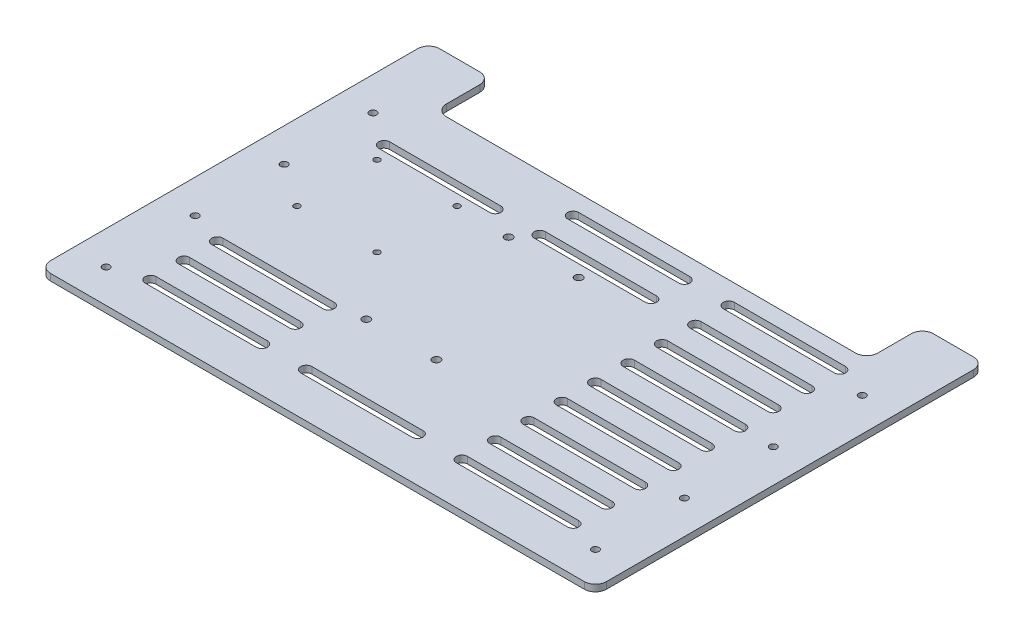
SolidWorks part; units mm, degrees
material "A-玻璃纤维"
ref_plane "前视基准面" through (0, 0, 0) normal (0, 0, 1) x (1, 0, 0)
ref_plane "上视基准面" through (0, 0, 0) normal (0, 1, 0) x (1, 0, 0)
ref_plane "右视基准面" through (0, 0, 0) normal (1, 0, 0) x (0, 0, -1)
other "Configuration Table"
sketch "草图1" plane through (0, 0, 0) normal (0, 1, 0) x (1, 0, 0)
  line L1 (-84.7342, 82.3595) -> (109.2658, 82.3595)
  line L2 (-112.7342, 55.552) -> (-112.7342, -67.6405)
  line L3 (-112.7342, -67.6405) -> (137.2658, -67.6405)
  line L4 (137.2658, 82.3595) -> (137.2658, -67.6405)
  line L5 (-112.7342, 55.552) -> (137.2658, -67.6405) construction
  line L6 (-112.7342, -67.6405) -> (137.2658, 82.3595) construction
  line L8 (-112.7342, 55.552) -> (-112.7342, 107.3595)
  line L9 (-112.7342, 107.3595) -> (-84.7342, 107.3595)
  line L10 (-84.7342, 82.3595) -> (-84.7342, 107.3595)
  line L12 (137.2658, 82.3595) -> (137.2658, 107.3595)
  line L13 (137.2658, 107.3595) -> (109.2658, 107.3595)
  line L14 (109.2658, 82.3595) -> (109.2658, 107.3595)
  point P0 (0, 0)
  dimension "D1" = 150
  dimension "D2" = 250
  dimension "D3" = 28
  dimension "D4" = 28
  dimension "D5" = 25
extrude "凸台-拉伸1" add sketch "草图1" along normal blind 3
fillet "圆角1" radius 5 8 edges at (137.2658, 1.5, 67.6405) (-112.7342, 1.5, 67.6405) (137.2658, 1.5, -107.3595) (109.2658, 1.5, -107.3595) (109.2658, 1.5, -82.3595) (-112.7342, 1.5, -107.3595) (-84.7342, 1.5, -107.3595) (-84.7342, 1.5, -82.3595)
sketch "草图4" plane through (0, 3, 0) normal (0, 1, 0) x (1, 0, 0)
  line L0 (57.2658, 72.3595) -> (107.2658, 72.3595) construction
  line L1 (57.2658, 74.8595) -> (107.2658, 74.8595)
  line L2 (57.2658, 69.8595) -> (107.2658, 69.8595)
  line L3 (57.2658, 57.3595) -> (107.2658, 57.3595) construction
  line L4 (104.2658, 82.3595) -> (-79.7342, 82.3595)
  line L5 (-112.7342, 102.3595) -> (-112.7342, -62.6405)
  line L6 (-107.7342, -67.6405) -> (132.2658, -67.6405)
  line L7 (137.2658, -62.6405) -> (137.2658, 102.3595)
  line L8 (104.2658, 82.3595) -> (-79.7342, 82.3595)
  line L9 (-112.7342, 102.3595) -> (-112.7342, -62.6405)
  line L11 (137.2658, -62.6405) -> (137.2658, 102.3595)
  line L12 (57.2658, 59.8595) -> (107.2658, 59.8595)
  line L13 (57.2658, 54.8595) -> (107.2658, 54.8595)
  line L14 (57.2658, 42.3595) -> (107.2658, 42.3595) construction
  line L15 (57.2658, 44.8595) -> (107.2658, 44.8595)
  line L16 (132.2658, 107.3595) -> (114.2658, 107.3595)
  line L17 (132.2658, 107.3595) -> (114.2658, 107.3595)
  line L18 (109.2658, 102.3595) -> (109.2658, 87.3595)
  line L19 (109.2658, 102.3595) -> (109.2658, 87.3595)
  line L20 (-84.7342, 87.3595) -> (-84.7342, 102.3595)
  line L21 (-84.7342, 87.3595) -> (-84.7342, 102.3595)
  line L22 (-89.7342, 107.3595) -> (-107.7342, 107.3595)
  line L23 (-89.7342, 107.3595) -> (-107.7342, 107.3595)
  line L24 (57.2658, 39.8595) -> (107.2658, 39.8595)
  line L25 (57.2658, 27.3595) -> (107.2658, 27.3595) construction
  line L26 (57.2658, 29.8595) -> (107.2658, 29.8595)
  line L27 (57.2658, 24.8595) -> (107.2658, 24.8595)
  line L28 (57.2658, 12.3595) -> (107.2658, 12.3595) construction
  line L29 (57.2658, 14.8595) -> (107.2658, 14.8595)
  line L30 (57.2658, 9.8595) -> (107.2658, 9.8595)
  line L31 (57.2658, -2.6405) -> (107.2658, -2.6405) construction
  line L32 (57.2658, -0.1405) -> (107.2658, -0.1405)
  line L33 (57.2658, -5.1405) -> (107.2658, -5.1405)
  line L34 (57.2658, -17.6405) -> (107.2658, -17.6405) construction
  line L35 (57.2658, -15.1405) -> (107.2658, -15.1405)
  line L36 (57.2658, -20.1405) -> (107.2658, -20.1405)
  line L37 (57.2658, -32.6405) -> (107.2658, -32.6405) construction
  line L38 (57.2658, -30.1405) -> (107.2658, -30.1405)
  line L39 (57.2658, -35.1405) -> (107.2658, -35.1405)
  line L40 (57.2658, -47.6405) -> (107.2658, -47.6405) construction
  line L41 (57.2658, -45.1405) -> (107.2658, -45.1405)
  line L42 (57.2658, -50.1405) -> (107.2658, -50.1405)
  line L52 (-12.7342, 72.3595) -> (37.2658, 72.3595) construction
  line L53 (-12.7342, 74.8595) -> (37.2658, 74.8595)
  line L54 (-12.7342, 69.8595) -> (37.2658, 69.8595)
  line L55 (-12.7342, 57.3595) -> (37.2658, 57.3595) construction
  line L56 (-12.7342, 59.8595) -> (37.2658, 59.8595)
  line L57 (-12.7342, 54.8595) -> (37.2658, 54.8595)
  line L58 (-82.7342, 72.3595) -> (-32.7342, 72.3595) construction
  line L59 (-82.7342, 74.8595) -> (-32.7342, 74.8595)
  line L60 (-82.7342, 69.8595) -> (-32.7342, 69.8595)
  line L61 (-82.7342, 57.3595) -> (-32.7342, 57.3595) construction
  line L62 (-82.7342, 59.8595) -> (-32.7342, 59.8595)
  line L63 (-82.7342, 54.8595) -> (-32.7342, 54.8595)
  line L64 (-12.7342, -47.6405) -> (37.2658, -47.6405) construction
  line L65 (-12.7342, -45.1405) -> (37.2658, -45.1405)
  line L66 (-12.7342, -50.1405) -> (37.2658, -50.1405)
  line L76 (-82.7342, -47.6405) -> (-32.7342, -47.6405) construction
  line L77 (-82.7342, -45.1405) -> (-32.7342, -45.1405)
  line L78 (-82.7342, -50.1405) -> (-32.7342, -50.1405)
  line L88 (-82.7342, -32.6405) -> (-32.7342, -32.6405) construction
  line L89 (-82.7342, -30.1405) -> (-32.7342, -30.1405)
  line L90 (-82.7342, -35.1405) -> (-32.7342, -35.1405)
  line L91 (-82.7342, -17.6405) -> (-32.7342, -17.6405) construction
  line L92 (-82.7342, -15.1405) -> (-32.7342, -15.1405)
  line L93 (-82.7342, -20.1405) -> (-32.7342, -20.1405)
  line L149 (57.2658, -77.6405) -> (107.2658, -77.6405) construction
  line L150 (57.2658, -75.1405) -> (107.2658, -75.1405)
  line L151 (57.2658, -80.1405) -> (107.2658, -80.1405)
  line L152 (57.2658, -92.6405) -> (107.2658, -92.6405) construction
  line L153 (57.2658, -90.1405) -> (107.2658, -90.1405)
  line L154 (57.2658, -95.1405) -> (107.2658, -95.1405)
  line L155 (57.2658, -62.6405) -> (107.2658, -62.6405) construction
  line L156 (57.2658, -60.1405) -> (107.2658, -60.1405)
  line L157 (57.2658, -65.1405) -> (107.2658, -65.1405)
  line L158 (57.2658, -77.6405) -> (107.2658, -77.6405) construction
  line L159 (57.2658, -75.1405) -> (107.2658, -75.1405)
  line L160 (57.2658, -80.1405) -> (107.2658, -80.1405)
  line L161 (57.2658, -92.6405) -> (107.2658, -92.6405) construction
  line L162 (57.2658, -90.1405) -> (107.2658, -90.1405)
  line L163 (57.2658, -95.1405) -> (107.2658, -95.1405)
  line L164 (57.2658, -62.6405) -> (107.2658, -62.6405) construction
  line L165 (57.2658, -60.1405) -> (107.2658, -60.1405)
  line L166 (57.2658, -65.1405) -> (107.2658, -65.1405)
  circle A0 centre (-18.8913, -14.5) radius 1.75 construction
  circle A1 centre (12.6087, -14.5) radius 1.75 construction
  circle A2 centre (-42.5828, 49.995) radius 1.35 construction
  circle A3 centre (-18.8913, 49.5) radius 1.75 construction
  arc A4 (57.2658, 74.8595) -> (57.2658, 69.8595) centre (57.2658, 72.3595) ccw
  arc A5 (-112.7342, -62.6405) -> (-107.7342, -67.6405) centre (-107.7342, -62.6405) ccw
  arc A6 (132.2658, -67.6405) -> (137.2658, -62.6405) centre (132.2658, -62.6405) ccw
  arc A7 (107.2658, 69.8595) -> (107.2658, 74.8595) centre (107.2658, 72.3595) ccw
  arc A9 (-112.7342, -62.6405) -> (-107.7342, -67.6405) centre (-107.7342, -62.6405) ccw
  arc A10 (132.2658, -67.6405) -> (137.2658, -62.6405) centre (132.2658, -62.6405) ccw
  circle A12 centre (12.6087, 49.5) radius 1.75 construction
  circle A13 centre (-18.8913, -14.5) radius 1.75
  circle A14 centre (12.6087, -14.5) radius 1.75
  circle A15 centre (-42.5828, 49.995) radius 1.35
  circle A16 centre (-18.8913, 49.5) radius 1.75
  circle A17 centre (12.6087, 49.5) radius 1.75
  circle A18 centre (-42.5828, 13.995) radius 1.35 construction
  circle A19 centre (-78.5828, 13.995) radius 1.35 construction
  circle A20 centre (-78.5828, 49.995) radius 1.35 construction
  circle A21 centre (-42.5828, 13.995) radius 1.35
  circle A22 centre (-78.5828, 13.995) radius 1.35
  circle A23 centre (-78.5828, 49.995) radius 1.35
  arc A24 (57.2658, 59.8595) -> (57.2658, 54.8595) centre (57.2658, 57.3595) ccw
  arc A25 (107.2658, 54.8595) -> (107.2658, 59.8595) centre (107.2658, 57.3595) ccw
  arc A26 (57.2658, 44.8595) -> (57.2658, 39.8595) centre (57.2658, 42.3595) ccw
  arc A27 (107.2658, 39.8595) -> (107.2658, 44.8595) centre (107.2658, 42.3595) ccw
  arc A28 (57.2658, 29.8595) -> (57.2658, 24.8595) centre (57.2658, 27.3595) ccw
  arc A29 (107.2658, 24.8595) -> (107.2658, 29.8595) centre (107.2658, 27.3595) ccw
  arc A30 (57.2658, 14.8595) -> (57.2658, 9.8595) centre (57.2658, 12.3595) ccw
  arc A32 (107.2658, 9.8595) -> (107.2658, 14.8595) centre (107.2658, 12.3595) ccw
  arc A34 (57.2658, -0.1405) -> (57.2658, -5.1405) centre (57.2658, -2.6405) ccw
  arc A36 (107.2658, -5.1405) -> (107.2658, -0.1405) centre (107.2658, -2.6405) ccw
  arc A38 (57.2658, -15.1405) -> (57.2658, -20.1405) centre (57.2658, -17.6405) ccw
  arc A40 (107.2658, -20.1405) -> (107.2658, -15.1405) centre (107.2658, -17.6405) ccw
  arc A42 (57.2658, -30.1405) -> (57.2658, -35.1405) centre (57.2658, -32.6405) ccw
  arc A43 (107.2658, -35.1405) -> (107.2658, -30.1405) centre (107.2658, -32.6405) ccw
  arc A44 (57.2658, -45.1405) -> (57.2658, -50.1405) centre (57.2658, -47.6405) ccw
  arc A45 (107.2658, -50.1405) -> (107.2658, -45.1405) centre (107.2658, -47.6405) ccw
  arc A52 (-12.7342, 74.8595) -> (-12.7342, 69.8595) centre (-12.7342, 72.3595) ccw
  arc A53 (37.2658, 69.8595) -> (37.2658, 74.8595) centre (37.2658, 72.3595) ccw
  arc A54 (-12.7342, 59.8595) -> (-12.7342, 54.8595) centre (-12.7342, 57.3595) ccw
  arc A55 (37.2658, 54.8595) -> (37.2658, 59.8595) centre (37.2658, 57.3595) ccw
  arc A56 (-82.7342, 74.8595) -> (-82.7342, 69.8595) centre (-82.7342, 72.3595) ccw
  arc A57 (-32.7342, 69.8595) -> (-32.7342, 74.8595) centre (-32.7342, 72.3595) ccw
  arc A58 (-82.7342, 59.8595) -> (-82.7342, 54.8595) centre (-82.7342, 57.3595) ccw
  arc A59 (-32.7342, 54.8595) -> (-32.7342, 59.8595) centre (-32.7342, 57.3595) ccw
  arc A60 (-12.7342, -45.1405) -> (-12.7342, -50.1405) centre (-12.7342, -47.6405) ccw
  arc A61 (37.2658, -50.1405) -> (37.2658, -45.1405) centre (37.2658, -47.6405) ccw
  arc A68 (-82.7342, -45.1405) -> (-82.7342, -50.1405) centre (-82.7342, -47.6405) ccw
  arc A69 (-32.7342, -50.1405) -> (-32.7342, -45.1405) centre (-32.7342, -47.6405) ccw
  arc A76 (-82.7342, -30.1405) -> (-82.7342, -35.1405) centre (-82.7342, -32.6405) ccw
  arc A77 (-32.7342, -35.1405) -> (-32.7342, -30.1405) centre (-32.7342, -32.6405) ccw
  arc A78 (-82.7342, -15.1405) -> (-82.7342, -20.1405) centre (-82.7342, -17.6405) ccw
  arc A79 (-32.7342, -20.1405) -> (-32.7342, -15.1405) centre (-32.7342, -17.6405) ccw
  arc A88 (137.2658, 102.3595) -> (132.2658, 107.3595) centre (132.2658, 102.3595) ccw
  arc A89 (137.2658, 102.3595) -> (132.2658, 107.3595) centre (132.2658, 102.3595) ccw
  arc A90 (114.2658, 107.3595) -> (109.2658, 102.3595) centre (114.2658, 102.3595) ccw
  arc A91 (114.2658, 107.3595) -> (109.2658, 102.3595) centre (114.2658, 102.3595) ccw
  arc A92 (104.2658, 82.3595) -> (109.2658, 87.3595) centre (104.2658, 87.3595) ccw
  arc A93 (104.2658, 82.3595) -> (109.2658, 87.3595) centre (104.2658, 87.3595) ccw
  arc A94 (-84.7342, 87.3595) -> (-79.7342, 82.3595) centre (-79.7342, 87.3595) ccw
  arc A95 (-84.7342, 87.3595) -> (-79.7342, 82.3595) centre (-79.7342, 87.3595) ccw
  arc A96 (-84.7342, 102.3595) -> (-89.7342, 107.3595) centre (-89.7342, 102.3595) ccw
  arc A97 (-84.7342, 102.3595) -> (-89.7342, 107.3595) centre (-89.7342, 102.3595) ccw
  arc A98 (-107.7342, 107.3595) -> (-112.7342, 102.3595) centre (-107.7342, 102.3595) ccw
  arc A99 (-107.7342, 107.3595) -> (-112.7342, 102.3595) centre (-107.7342, 102.3595) ccw
  arc A140 (57.2658, -75.1405) -> (57.2658, -80.1405) centre (57.2658, -77.6405) ccw
  arc A141 (107.2658, -80.1405) -> (107.2658, -75.1405) centre (107.2658, -77.6405) ccw
  arc A142 (57.2658, -90.1405) -> (57.2658, -95.1405) centre (57.2658, -92.6405) ccw
  arc A143 (107.2658, -95.1405) -> (107.2658, -90.1405) centre (107.2658, -92.6405) ccw
  arc A144 (57.2658, -60.1405) -> (57.2658, -65.1405) centre (57.2658, -62.6405) ccw
  arc A145 (107.2658, -65.1405) -> (107.2658, -60.1405) centre (107.2658, -62.6405) ccw
  point P38 (82.2658, 72.3595)
  point P47 (82.2658, 57.3595)
  point P54 (82.2658, 42.3595)
  point P61 (82.2658, 27.3595)
  point P68 (82.2658, 12.3595)
  point P75 (82.2658, -2.6405)
  point P82 (82.2658, -17.6405)
  point P89 (82.2658, -32.6405)
  point P96 (82.2658, -47.6405)
  point P103 (82.2658, -82.6405)
  point P110 (82.2658, -97.6405)
  point P124 (12.2658, 72.3595)
  point P131 (12.2658, 57.3595)
  point P138 (-57.7342, 72.3595)
  point P145 (-57.7342, 57.3595)
  point P152 (12.2658, -47.6405)
  point P159 (12.2658, -82.6405)
  point P166 (12.2658, -97.6405)
  point P173 (82.2658, -67.6405)
  point P180 (-57.7342, -47.6405)
  point P187 (-57.7342, -82.6405)
  point P194 (-57.7342, -97.6405)
  point P201 (12.2658, -67.6405)
  point P208 (-57.7342, -32.6405)
  point P215 (-57.7342, -17.6405)
  point P220 (-57.7342, -67.6405)
  point P272 (82.2658, -82.6405)
  point P279 (82.2658, -97.6405)
  point P286 (82.2658, -67.6405)
  point P293 (82.2658, -82.6405)
  point P300 (82.2658, -97.6405)
  point P307 (82.2658, -67.6405)
  point P314 (82.2658, -82.6405)
  point P321 (82.2658, -97.6405)
  point P328 (82.2658, -67.6405)
  point P335 (82.2658, -77.6405)
  point P342 (82.2658, -92.6405)
  point P349 (82.2658, -62.6405)
  point P356 (82.2658, -77.6405)
  point P363 (82.2658, -92.6405)
  point P370 (82.2658, -62.6405)
  point P377 (82.2658, -77.6405)
  point P384 (82.2658, -92.6405)
  point P391 (82.2658, -62.6405)
  dimension "D4" = 2.5
  dimension "D2" = 30
  dimension "D3" = 50
  dimension "D5" = 10
  dimension "D1" = 0
  dimension "D6" = 12
  dimension "D7" = 3
  dimension "D8" = 3
  dimension "D9" = 3
extrude "切除-拉伸2" cut sketch "草图4" against normal blind 10 contours A17 | A13 | A15 | A22 | A21 | A14 | A16 | A23 region at (-18.8913, 3, 14.5) region at (-42.5828, 3, -49.995) region at (12.6087, 3, -49.5) region at (-42.5828, 3, -13.995) region at (-78.5828, 3, -13.995)
extrude "切除-拉伸3" cut sketch "草图4<3>" against normal blind 10 contours L63 A59 L62 A58 | L54 A53 L53 A52 | L57 A55 L56 A54 | L93 A79 L92 A78 | L90 A77 L89 A76 | L78 A69 L77 A68 | L66 A61 L65 A60 | L42 A45 L41 A44 | L39 A43 L38 A42 | L36 A40 L35 A38 | L33 A36 L32 A34 | L30 A32 L29 A30 | L27 A29 L26 A28 | L24 A27 L15 A26 | L13 A25 L12 A24 | L2 A7 L1 A4
sketch "草图4<3>" plane through (0, 3, 0) normal (0, 1, 0) x (1, 0, 0) same geometry as "草图4"
sketch "草图5" plane through (0, 3, 0) normal (0, 1, 0) x (1, 0, 0)
  line L0 (12.2658, 82.3595) -> (12.2658, -94.0338) construction
  line L1 (104.2658, 82.3595) -> (-79.7342, 82.3595) construction
  line L2 (-112.7342, 102.3595) -> (-112.7342, -62.6405) construction
  line L3 (-89.7342, 107.3595) -> (-107.7342, 107.3595) construction
  circle A0 centre (-97.7342, 67.3595) radius 1.6
  circle A1 centre (-97.7342, 27.3595) radius 1.6
  circle A2 centre (-97.7342, -12.6405) radius 1.6
  circle A3 centre (-97.7342, -52.6405) radius 1.6
  circle A4 centre (122.2658, -52.6405) radius 1.6
  circle A5 centre (122.2658, -12.6405) radius 1.6
  circle A6 centre (122.2658, 27.3595) radius 1.6
  circle A7 centre (122.2658, 67.3595) radius 1.6
  dimension "D1" = 3.2
  dimension "D2" = 15
  dimension "D3" = 40
  dimension "D5" = 40
  dimension "D4" = 4
extrude "切除-拉伸4" cut sketch "草图5" against normal blind 10
